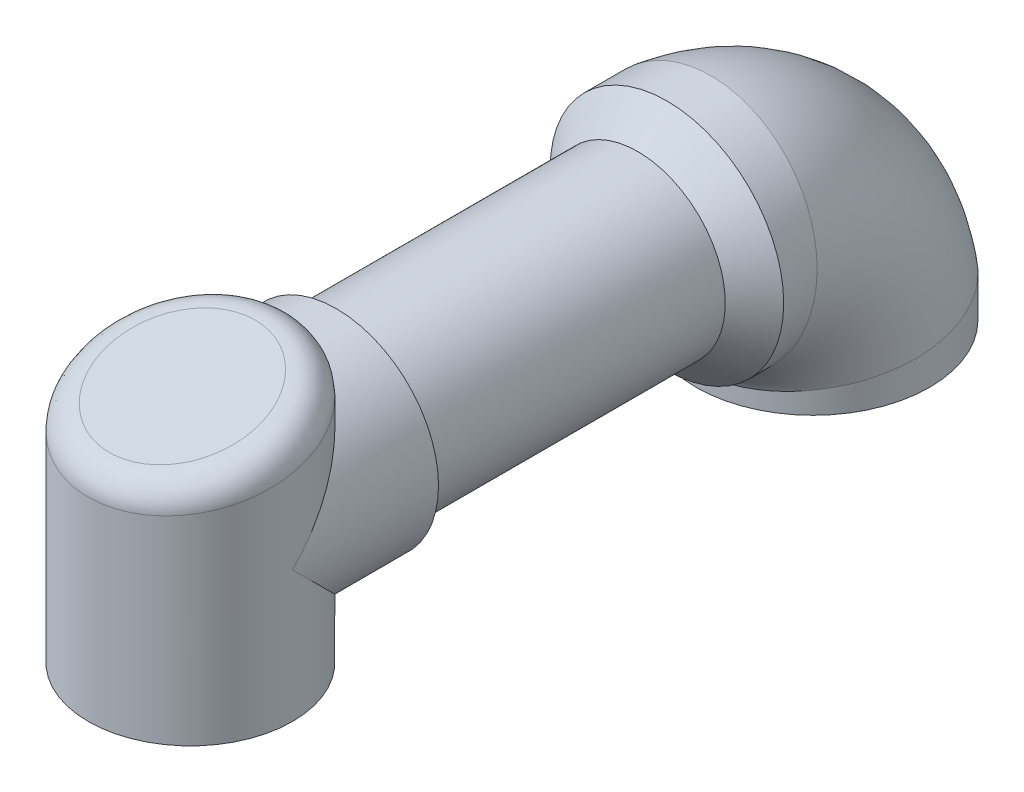
SolidWorks part; units mm, degrees
ref_plane "Front Plane" through (0, 0, 0) normal (0, 0, 1) x (1, 0, 0)
ref_plane "Top Plane" through (0, 0, 0) normal (0, 1, 0) x (1, 0, 0)
ref_plane "Right Plane" through (0, 0, 0) normal (1, 0, 0) x (0, 0, -1)
sketch "Sketch1" plane through (0, 0, 0) normal (0, 1, 0) x (1, 0, 0)
  circle A0 centre (0, 0) radius 40
  dimension "D1" = 80
ref_plane "Plane1" through (0, 0, 50) normal (0, 0, 1) x (1, 0, 0)
sketch "Sketch2" plane through (0, 0, 50) normal (0, 0, 1) x (1, 0, 0)
  circle A0 centre (0, 50) radius 40
  dimension "D1" = 80
  dimension "D2" = 50
sketch "Sketch3" plane through (0, 0, 0) normal (1, 0, 0) x (0, 0, -1)
  line L0 (40, 0) -> (40, 15)
  line L1 (40, 0) -> (-40, 0) construction
  line L2 (-50, 90) -> (-35, 90)
  line L3 (-50, 90) -> (-50, 10) construction
  line L4 (-50, 48.8466) -> (-50, -48.8466) construction
  line L5 (40, 0) -> (-40, 0)
  line L7 (-50, 10) -> (-50, 90)
  arc A0 (-35, 90) -> (40, 15) centre (-50, 0) cw
  arc A1 (-50, 10) -> (-40, 0) centre (-50, 0) cw
  point P8 (-50, 0)
  dimension "D1" = 15
  dimension "D2" = 40
  dimension "D3" = 90
  dimension "D4" = 10
  dimension "D5" = 10
sweep "Sweep1" add profiles "Sketch2" path "Sketch3"
sketch "Sketch4" plane through (0, 0, 50) normal (0, 0, 1) x (1, 0, 0)
  circle A0 centre (0, 50) radius 30
  dimension "D1" = 60
extrude "Boss-Extrude1" add sketch "Sketch4" along normal blind 113.25
chamfer "Chamfer1" distance 10 angle 45 1 edges at (30, 50, 50)
ref_plane "Plane2" through (0, 50, 0) normal (0, 1, 0) x (1, 0, 0)
sketch "Sketch6" plane through (0, 0, 163.25) normal (0, 0, 1) x (1, 0, 0)
  circle A0 centre (0, 50) radius 35
  dimension "D1" = 70
extrude "Boss-Extrude2" add sketch "Sketch6" along normal blind 50
sketch "Sketch7" plane through (0, 50, 0) normal (0, 1, 0) x (1, 0, 0)
  line L0 (-35, -213.25) -> (35, -213.25) construction
  circle A0 centre (0, -213.25) radius 35
extrude "Boss-Extrude3" add sketch "Sketch7" along normal blind 49.1 and the other way blind 45
sketch "Sketch8" plane through (0, 0, 0) normal (1, 0, 0) x (0, 0, -1)
  line L0 (-178.25, 99.1) -> (-248.25, 99.1)
  line L1 (-248.25, 99.1) -> (-248.25, 79.1)
  line L2 (-248.25, 99.1) -> (-248.25, 5) construction
  line L3 (-248.25, 79.1) -> (-178.25, 99.1)
  dimension "D1" = 20
extrude "Cut-Extrude1" cut sketch "Sketch8" against normal through all both and the other way through all
fillet "Fillet1" radius 10 1 edges at (0, 99.1, 178.25)
ref_plane "Plane3" through (0, 50, 0) normal (0, -1, 0) x (-1, 0, 0)
sketch "Sketch9" plane through (0, 50, 0) normal (0, -1, 0) x (-1, 0, 0)
  line L0 (35, -213.25) -> (-35, -213.25) construction
  line L1 (0, -248.25) -> (0, -178.25) construction
  circle A0 centre (0, -213.25) radius 35 construction
  point P7 (0, -213.25)
